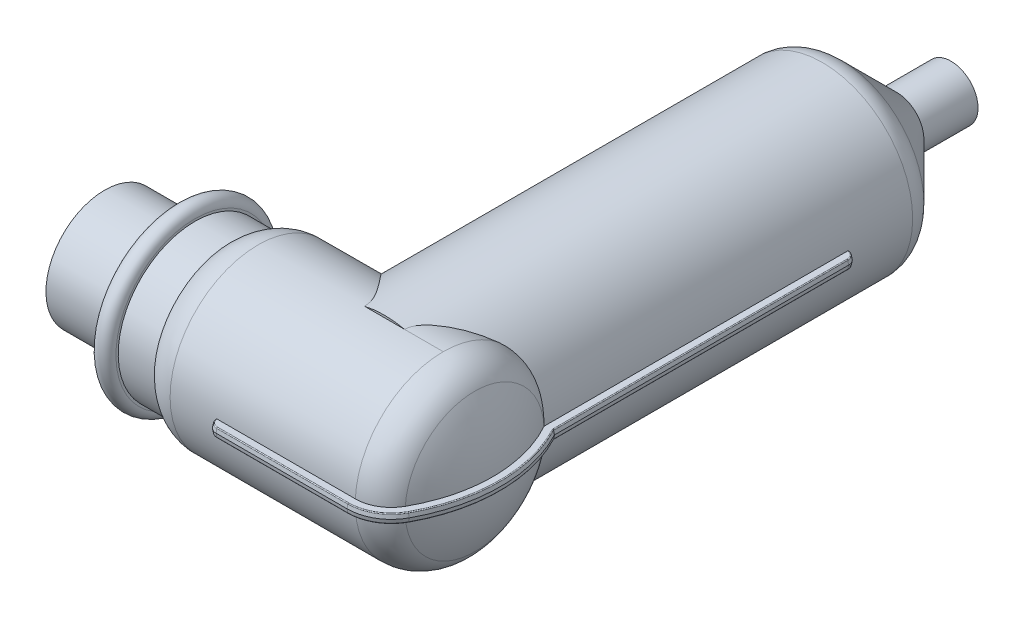
SolidWorks part; units mm, degrees
ref_plane "Front Plane" through (0, 0, 0) normal (0, 0, 1) x (1, 0, 0)
ref_plane "Top Plane" through (0, 0, 0) normal (0, 1, 0) x (1, 0, 0)
ref_plane "Right Plane" through (0, 0, 0) normal (1, 0, 0) x (0, 0, -1)
sketch "Sketch1" plane through (0, 0, 0) normal (0, 0, 1) x (1, 0, 0)
  line L0 (8, 6.5) -> (8, 8.75)
  line L2 (10, 8.75) -> (10, 8.5)
  line L3 (10, 8.5) -> (14, 8.5)
  line L4 (0, 0) -> (43, 0)
  line L5 (37.5, 9.75) -> (17, 9.75)
  line L6 (0, 0) -> (-5.7927, 0) construction
  line L7 (43, 0) -> (43, 7.3633) construction
  line L8 (8, 6.5) -> (0, 6.5)
  line L9 (0, 6.5) -> (0, 0)
  arc A0 (8, 8.75) -> (10, 8.75) centre (9, 8.75) cw
  arc A1 (17, 9.75) -> (14, 8.5) centre (17, 5.525) ccw
  arc A2 (43, 0) -> (40.9903, 7.704) centre (27.2292, 0) ccw
  arc A3 (37.5, 9.75) -> (40.9903, 7.704) centre (37.5, 5.75) cw
  dimension "D9" = 4
  dimension "D1" = 2
  dimension "D2" = 17.5
  dimension "D3" = 6
  dimension "D4" = 9
  dimension "D5" = 17
  dimension "D6" = 35
  dimension "D7" = 29.5
  dimension "D8" = 19.5
  dimension "D10" = 13
  dimension "D11" = 8
revolve "Revolve1" add sketch "Sketch1" angle 360 about L6
sketch "Sketch2" plane through (0, 0, 0) normal (0, 1, 0) x (1, 0, 0)
  line L0 (31, 0) -> (31, -17.9723) construction
  line L1 (31, 0) -> (0, 0) construction
  line L2 (41, 0) -> (31, 0)
  line L3 (31, 0) -> (31, 62.7426)
  line L4 (31, 62.7426) -> (34, 62.7426)
  line L5 (34, 62.7426) -> (34, 56.7426)
  line L6 (34, 56.7426) -> (40.1213, 50.6213)
  line L7 (41, 48.5) -> (41, 0)
  arc A0 (40.1213, 50.6213) -> (41, 48.5) centre (38, 48.5) cw
  dimension "D6" = 6
  dimension "D5" = 3
  dimension "D1" = 31
  dimension "D2" = 45
  dimension "D3" = 48.5
  dimension "D4" = 20
  dimension "D8" = 6
revolve "Revolve2" add sketch "Sketch2" angle 360 about L0
sketch "Sketch3" plane through (0, 0, 0) normal (0, 1, 0) x (1, 0, 0)
  line L0 (37.5, 6.1084) -> (37.5, -9.75) construction
  line L1 (40.9, 7.661) -> (40.9, 41.5)
  line L2 (0, 0) -> (43, 0) construction
  line L3 (22, -9.65) -> (37.5, -9.65)
  line L4 (31, 0) -> (31, 62.7426) construction
  line L5 (21.1, 9.65) -> (19, 9.65)
  line L7 (21.1, 41.5) -> (21.1, 9.65)
  line L8 (21, 48.5) -> (41, 48.5) construction
  line L9 (17, -9.75) -> (17, 9.75) construction
  line L10 (23, -10.65) -> (37.5, -10.65)
  line L11 (41.9, 7.9136) -> (41.9, 40.5)
  line L12 (20.1, 40.5) -> (20.1, 10.65)
  line L13 (20.1, 10.65) -> (20, 10.65)
  line L14 (41.9, 7.9136) -> (41.9, 41.5) construction
  line L15 (20.1, 41.5) -> (20.1, 10.65) construction
  line L16 (20.1, 10.65) -> (19, 10.65) construction
  line L17 (22, -10.65) -> (37.5, -10.65) construction
  line L18 (31, 0) -> (0, 0) construction
  arc A0 (40.9231, -7.6187) -> (40.9, 7.661) centre (26.9673, 0) ccw construction
  arc A1 (40.9231, -7.6187) -> (40.9, 7.661) centre (26.9673, 0) ccw
  arc A3 (37.5, -9.65) -> (40.9231, -7.6187) centre (37.5, -5.75) ccw
  arc A4 (37.5, -10.65) -> (41.8008, -8.0979) centre (37.5, -5.75) ccw
  arc A5 (41.8008, -8.0979) -> (41.9, 7.9136) centre (26.9673, 0) ccw
  arc A6 (41.9, 40.5) -> (40.9, 41.5) centre (40.9, 40.5) ccw
  arc A7 (20.1, 40.5) -> (21.1, 41.5) centre (21.1, 40.5) cw
  arc A8 (20, 10.65) -> (19, 9.65) centre (20, 9.65) ccw
  arc A9 (23, -10.65) -> (22, -9.65) centre (23, -9.65) cw
  dimension "D11" = 3.9
  dimension "D12" = 15.9
  dimension "D1" = 7
  dimension "D2" = 7
  dimension "D3" = 2
  dimension "D4" = 5
  dimension "D7" = 9.9
  dimension "D8" = 9.65
  dimension "D9" = 9.9
  dimension "D10" = 9.65
  dimension "D5" = 1
  dimension "D6" = 1
extrude "Boss-Extrude1" add sketch "Sketch3" along normal mid plane 1 draft 10
fillet "Fillet1" radius 0.1 24 edges at (20.4248, 0.5, -41.1128) (20.4248, -0.5, -41.1128) (20.1882, 0.5, -25.5309) (20.1882, -0.5, -25.5309) (19.3872, -0.5, -10.3252) (20.0941, 0.5, -10.5618) (41.5752, 0.5, -41.1128) (22.3872, 0.5, 10.3252) (30.25, 0.5, 10.5618) (39.9555, 0.5, 9.8881) (41.5752, -0.5, -41.1128) (43.7789, -0.5, 0.0932) (39.9555, -0.5, 9.8881) (30.25, -0.5, 10.5618) (20.0941, -0.5, -10.5618) (20.1441, -0.25, -10.6059) (20.1441, 0.25, -10.6059) (19.3872, 0.5, -10.3252) (41.8118, 0.5, -24.1958) (43.7789, 0.5, 0.0932) (41.8118, -0.5, -24.1958) (22.3872, -0.5, 10.3252)
